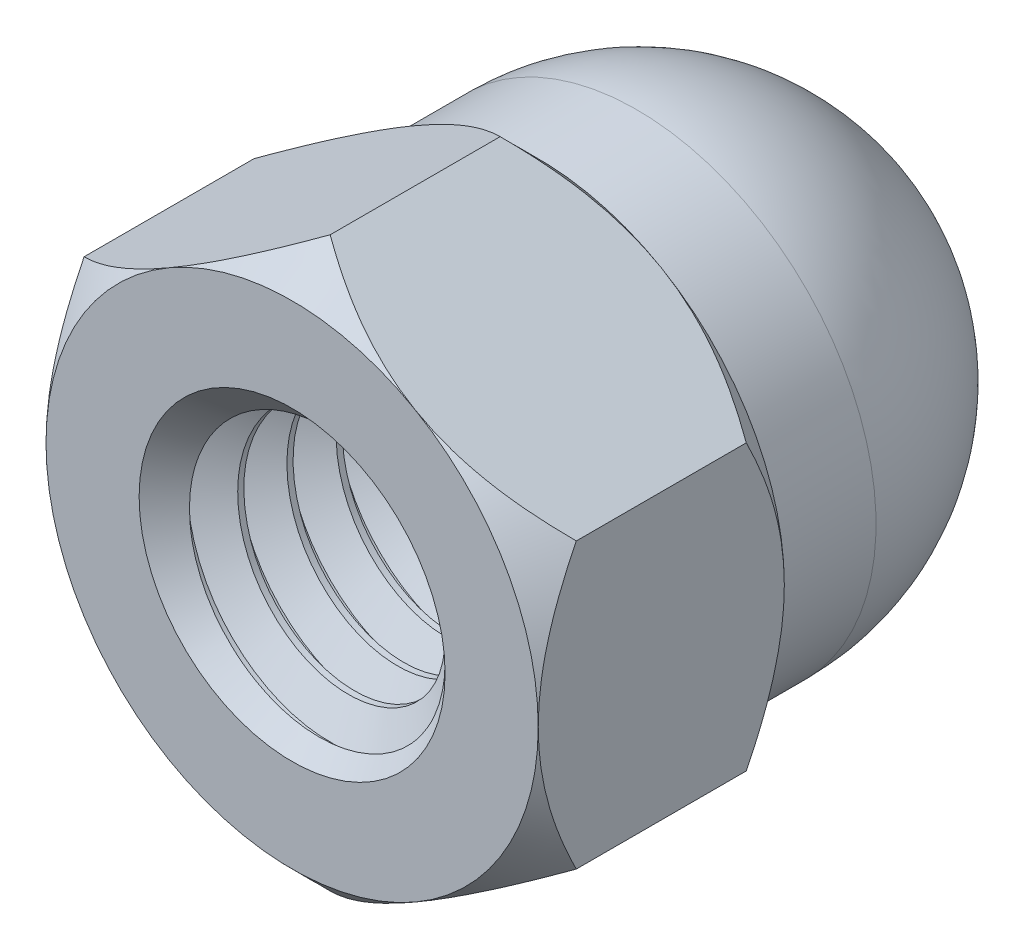
SolidWorks part; units mm, degrees
ref_plane "Front Plane" through (0, 0, 0) normal (0, 0, 1) x (1, 0, 0)
ref_plane "Top Plane" through (0, 0, 0) normal (0, 1, 0) x (1, 0, 0)
ref_plane "Right Plane" through (0, 0, 0) normal (1, 0, 0) x (0, 0, -1)
sketch "Sketch1" plane through (0, 0, 0) normal (-1, 0, 0) x (0, 0, 1)
  line L0 (-6, 0) -> (6, 0) construction
  line L1 (-6, 0) -> (-6, 5) construction
  line L2 (6, 5) -> (-6, 5) construction
  line L3 (6, 3) -> (-1.71, 3) construction
  line L4 (6, 0) -> (6, 5) construction
  line L5 (-1.71, 3) -> (-1.71, 0) construction
  line L7 (-1.71, 3) -> (-2.5138, 0) construction
  line L8 (6.9375, 3.1083) -> (6.4375, 2.2422) construction
  line L9 (6.4375, 2.2422) -> (5.9375, 3.1083) construction
  line L10 (5.9375, 3.1083) -> (6.9375, 3.1083) construction
  line L11 (6.4375, 2.2422) -> (6.4375, 2.3505) construction
  line L12 (6.4375, 3.1083) -> (6.4375, 3) construction
  line L13 (6.875, 3) -> (6, 3) construction
  line L14 (6.375, 2.3505) -> (6.5, 2.3505) construction
  line L15 (6.4375, 3.0541) -> (5.9687, 3.0541) construction
  line L16 (6.4375, 3.0541) -> (6.9062, 3.0541) construction
  arc A2 (-6, 0) -> (-1, 5) centre (-1, 0) cw construction
  point P3 (0, 0)
  point P23 (1, 5)
  dimension "Height" = 12
  dimension "Width" = 10
  dimension "Thread Depth" = 7.71
  dimension "Thread OD" = 6
  dimension "Thread Tip Angle" = 75
  dimension "Thread Pitch" = 1
  dimension "D1" = 0.125
  dimension "Hex Thickness (m)" = 5
ref_plane "Plane1" through (0, 0, 6) normal (0, 0, 1) x (1, 0, 0)
ref_plane "Plane2" through (0, 0, 1) normal (0, 0, 1) x (1, 0, 0)
ref_plane "Plane3" through (0, 0, -1.71) normal (0, 0, 1) x (1, 0, 0)
sketch "Sketch7" plane through (0, 0, 6) normal (0, 0, 1) x (1, 0, 0)
  line L1 (0, 5.7735) -> (-5, 2.8868)
  line L2 (-5, 2.8868) -> (-5, -2.8868)
  line L3 (-5, -2.8868) -> (0, -5.7735)
  line L4 (0, -5.7735) -> (5, -2.8868)
  line L5 (5, -2.8868) -> (5, 2.8868)
  line L6 (5, 2.8868) -> (0, 5.7735)
  circle A0 centre (0, 0) radius 5 construction
  point P0 (0, 5)
extrude "Boss-Extrude2" add sketch "Sketch7" against normal up to vertex (5 mm away) up to point (0, 5, 1)
sketch "Sketch8" plane through (0, 0, 6) normal (0, 0, 1) x (1, 0, 0)
  circle A0 centre (0, 0) radius 5
extrude "Cut-Extrude3" cut sketch "Sketch8" against normal through all draft 45 flip side to cut
sketch "Sketch9" plane through (0, 0, 1) normal (0, 0, 1) x (1, 0, 0)
  circle A1 centre (0, 0) radius 5
  circle A2 centre (0, 0) radius 5
  dimension "D1" = 0
extrude "Cut-Extrude4" cut sketch "Sketch9" along normal through all draft 45 flip side to cut
sketch "Sketch10" plane through (0, 0, 0) normal (1, 0, 0) x (0, 0, -1)
  line L0 (1, 5) -> (-1, 5)
  line L1 (6, 0) -> (-6, 0) construction
  line L3 (6, 0) -> (-1, 0)
  line L4 (-1, 5) -> (-1, 0)
  arc A0 (6, 0) -> (1, 5) centre (1, 0) ccw construction
  arc A4 (6, 0) -> (1, 5) centre (1, 0) ccw
revolve "Revolve1" add sketch "Sketch10" angle 360 about L0
sketch "Sketch16" plane through (0, 0, 0) normal (0, 0, 1) x (1, 0, 0)
  line L0 (0, 0) -> (0, -3) construction
  line L1 (0, 0) -> (1.1481, -2.7716) construction
  circle A0 centre (0, 0) radius 3 construction
  point P3 (1.1481, -2.7716)
  dimension "D1" = 22.5
sketch "Sketch17" plane through (0, 0, 0) normal (1, 0, 0) x (0, 0, -1)
  line L0 (1.71, 3) -> (2.5138, 0) construction
  line L1 (-6, 3) -> (1.71, 3) construction
  line L2 (1.71, 3) -> (2.5138, 0)
  line L3 (-6, 3) -> (1.71, 3)
  line L4 (2.5138, 0) -> (1.71, -3)
  line L5 (1.71, -3) -> (-6, -3)
sketch "Sketch11" plane through (0, 0, 0) normal (1, 0, 0) x (0, 0, -1)
  line L2 (-6, 0) -> (-6, 5) construction
  line L3 (-6, 3) -> (1.71, 3) construction
  line L6 (-6, 0) -> (-6, 3)
  line L7 (-6, 3) -> (1.71, 3)
  line L8 (1.71, 3) -> (2.5138, 0) construction
  line L9 (1.71, 3) -> (2.5138, 0)
  line L10 (6, 0) -> (-6, 0) construction
  line L11 (2.5138, 0) -> (-6, 0)
revolve "Cut-Revolve1" cut sketch "Sketch11" angle 360 about L0
sketch "Sketch12" plane through (0, 0, 6) normal (0, 0, 1) x (1, 0, 0)
  circle A0 centre (0, 0) radius 3
  point P0 (0, 3)
curve "Helix/Spiral1" pitch 1 height 8.71 turns 8.71
sketch "Sketch13" plane through (0, 0, 0) normal (1, 0, 0) x (0, 0, -1)
  line L0 (-6.9062, 3.0541) -> (-6.5, 2.3505)
  line L1 (-6.5, 2.3505) -> (-6.375, 2.3505)
  line L2 (-6.375, 2.3505) -> (-5.9687, 3.0541)
  line L3 (-5.9687, 3.0541) -> (-6.9062, 3.0541)
sweep "Sweep1" add profiles "Sketch13" path "Helix/Spiral1"
sketch "Sketch14" plane through (0, 0, 0) normal (1, 0, 0) x (0, 0, -1)
  line L0 (6, 0) -> (6, 5) construction
  line L1 (1, 4.8629) -> (-1, 4.8629)
  line L2 (6, 1.5) -> (6, 5) construction
  line L4 (6, 1.5) -> (5.7258, 1.5) construction
  line L5 (1.71, 3) -> (1.71, 0) construction
  line L7 (6.2742, 5) -> (6.2742, 1.5)
  line L8 (6.2742, 1.5) -> (6, 1.5) construction
  line L10 (6.2742, 1.5) -> (6.2742, 0)
  line L12 (6.2742, 0) -> (6, 0)
  line L13 (6, 0) -> (-6, 0) construction
  line L14 (6, 5) -> (1, 5)
  line L15 (6, 5) -> (6.2742, 5)
  line L17 (1, 5) -> (1, 4.7258) construction
  line L21 (6, 0) -> (6, -2.8136) construction
  line L22 (-6, 5) -> (6, 5) construction
  line L23 (-1, 5) -> (-1, 4.3301) construction
  line L24 (1, 5) -> (-1, 5)
  line L25 (-1, 5) -> (-1, 4.8629)
  line L26 (1, 5) -> (1, -5) construction
  arc A0 (6, 0) -> (1, 4.8629) centre (1, -0.1391) ccw
  point P9 (1.71, 1.5)
revolve "Cut-Revolve4" cut sketch "Sketch14" angle 360 about L0
sketch "Sketch15" plane through (0, 0, 6) normal (0, 0, 1) x (1, 0, 0)
  circle A0 centre (0, 0) radius 3.1083
extrude "Cut-Extrude5" cut sketch "Sketch15" against normal through all draft 45 and the other way through all draft 45
equation "\"D1@Sketch1\" = \"Thread Pitch@Sketch1\" / 8"
equation "\"D3@Helix/Spiral1\" = \"Thread Depth@Sketch1\" + \"Thread Pitch@Sketch1\""
equation "\"D4@Helix/Spiral1\" = \"Thread Pitch@Sketch1\""
